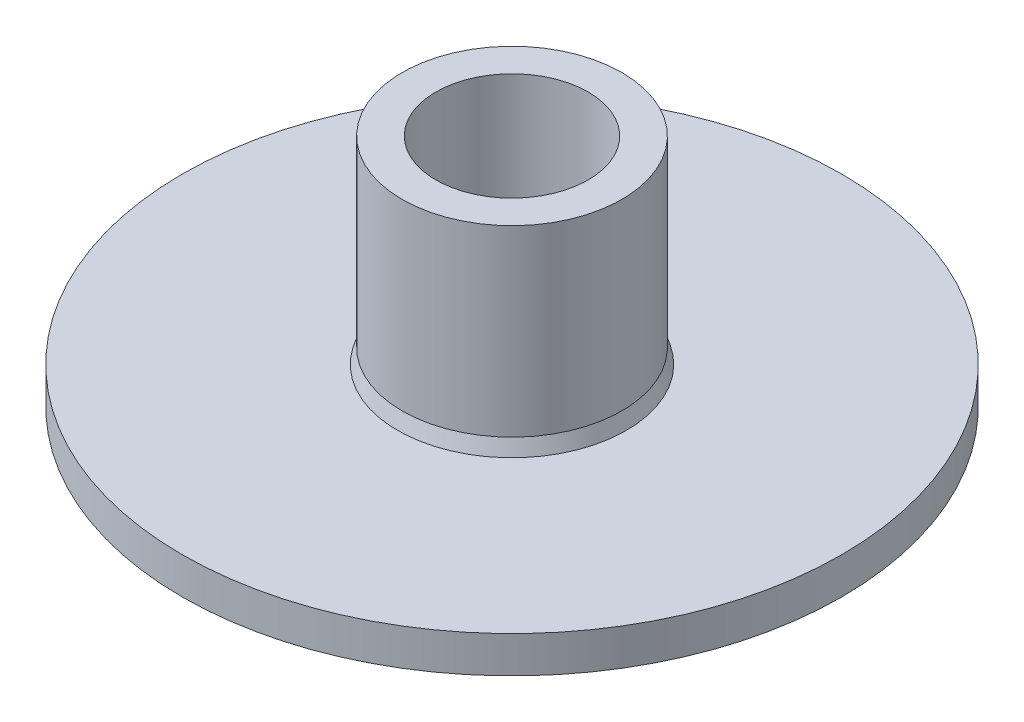
SolidWorks part; units mm, degrees
material "6061-T6 (SS)"
ref_plane "Piano frontale" through (0, 0, 0) normal (0, 0, 1) x (1, 0, 0)
ref_plane "Piano superiore" through (0, 0, 0) normal (0, 1, 0) x (1, 0, 0)
ref_plane "Piano destro" through (0, 0, 0) normal (1, 0, 0) x (0, 0, -1)
sketch "Schizzo1" plane through (0, 0, 0) normal (0, 0, 1) x (1, 0, 0)
  line L0 (0, 0) -> (0, 31.7802) construction
  line L2 (-68, 0) -> (-68, 5)
  line L3 (-68, 5) -> (-15.6118, 5)
  line L4 (-15.6118, 5) -> (-15, 7)
  line L5 (-15, 7) -> (-15, 32)
  line L6 (-15, 32) -> (-10.4, 32)
  line L7 (-10.4, 32) -> (-10.4, 8.5)
  line L8 (-10.4, 8.5) -> (-13, 0)
  line L9 (-13, 0) -> (-24, 0)
  line L11 (-24, 0) -> (-68, 0)
  line L12 (-18.4, 0) -> (-18.4, 1.3)
  line L13 (-18.4, 1.3) -> (-16, 1.3)
  line L14 (-16, 1.3) -> (-16, 0)
  line L15 (-34.4, 0) -> (-34.4, 1.3)
  line L16 (-34.4, 1.3) -> (-32, 1.3)
  line L17 (-32, 1.3) -> (-32, 0)
  line L18 (-68, 0) -> (-68, 26) construction
  line L21 (-29.5, 0) -> (-29.5, 1.3)
  line L23 (-29.5, 1.3) -> (-27.1, 1.3)
  line L24 (-27.1, 1.3) -> (-27.1, 0)
  line L25 (-45, 0) -> (-45, 5)
  point P3 (-10.4, 20.25)
  dimension "D2" = 26
  dimension "D3" = 20.8
  dimension "D5" = 5
  dimension "D7" = 30
  dimension "D8" = 25
  dimension "D9" = 27
  dimension "D10" = 8.5
  dimension "D11" = 2.4
  dimension "D12" = 1.3
  dimension "D13" = 32
  dimension "D14" = 64
  dimension "D15" = 2.5
  dimension "D16" = 90
revolve "Rivoluzione1" add sketch "Schizzo1" angle 360 about L0 region at (-44.5287, 2.5, 0)
fillet "Raccordo2" radius 0.2 6 edges at (0, 1.3, -18.4) (0, 1.3, -16) (0, 1.3, -29.5) (0, 1.3, -27.1) (0, 1.3, -34.4) (0, 1.3, -32)
